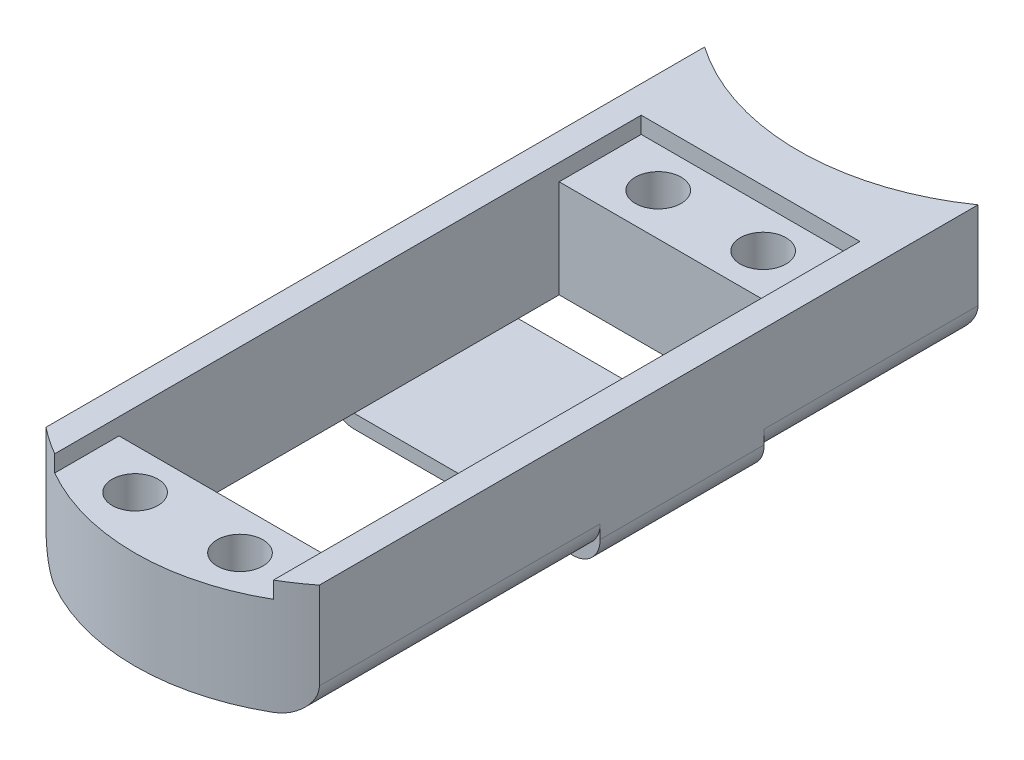
SolidWorks part; units mm, degrees
ref_plane "Front Plane" through (0, 0, 0) normal (0, 0, 1) x (1, 0, 0)
ref_plane "Top Plane" through (0, 0, 0) normal (0, 1, 0) x (1, 0, 0)
ref_plane "Right Plane" through (0, 0, 0) normal (1, 0, 0) x (0, 0, -1)
sketch "Sketch1" plane through (0, 0, 0) normal (0, 1, 0) x (1, 0, 0)
  circle A0 centre (0, 0) radius 20.3708 construction
  circle A1 centre (0, 0) radius 20.3708 construction
sketch "Sketch2" plane through (0, 0, 0) normal (0, 1, 0) x (1, 0, 0)
  line L0 (-12.7, 45.261) -> (-12.7, -15.9273)
  line L1 (-12.7, -8.89) -> (-12.7, -15.9273) construction
  line L2 (12.7, 45.261) -> (12.7, -15.9273)
  line L3 (-10.16, 29.21) -> (10.16, 29.21)
  line L4 (10.16, 29.21) -> (10.16, -17.6563)
  line L5 (-10.16, 29.21) -> (-10.16, -17.6563)
  circle A0 centre (0, 0) radius 20.3708 construction
  arc A1 (-10.16, -17.6563) -> (-12.7, -15.9273) centre (0, 0) cw
  arc A2 (10.16, -17.6563) -> (12.7, -15.9273) centre (0, 0) ccw
  arc A3 (-12.7, 45.261) -> (12.7, 45.261) centre (0, 63.5) ccw
  arc A4 (12.7, 45.261) -> (-12.7, 45.261) centre (0, 63.5) ccw construction
  point P27 (-10.16, -17.6563)
extrude "Boss-Extrude1" add sketch "Sketch2" against normal blind 10.6502
sketch "Sketch3" plane through (0, 0, 0) normal (0, 1, 0) x (1, 0, 0)
  line L1 (-10.16, 36.83) -> (10.16, 36.83)
  line L2 (-10.16, 36.83) -> (-10.16, 29.21)
  line L3 (-10.16, 29.21) -> (10.16, 29.21)
  line L4 (10.16, 36.83) -> (10.16, 29.21)
extrude "Cut-Extrude1" cut sketch "Sketch3" against normal blind 1.5494
sketch "Sketch4" plane through (0, -1.5494, 0) normal (0, 1, 0) x (1, 0, 0)
  circle A0 centre (-4.8743, 33.1241) radius 2.126
  circle A1 centre (4.8743, 33.1241) radius 2.126
  dimension "D1" = 4.252
  dimension "D2" = 4.252
extrude "Cut-Extrude2" cut sketch "Sketch4" against normal blind 19.3294
sketch "Sketch5" plane through (0, -1.5494, 0) normal (0, 1, 0) x (1, 0, 0)
  line L3 (10.16, -11.684) -> (-10.16, -11.684)
  line L12 (-10.16, -11.684) -> (-10.16, -17.6563)
  line L13 (10.16, -17.6563) -> (10.16, -11.684)
  line L14 (10.16, -11.684) -> (-10.16, -11.684)
  line L15 (-10.16, -11.684) -> (-10.16, -17.6563)
  line L16 (10.16, -17.6563) -> (10.16, -11.684)
  circle A0 centre (4.8743, -15.4762) radius 2.126 construction
  arc A1 (-10.16, -17.6563) -> (10.16, -17.6563) centre (0, 0) ccw
  arc A2 (-10.16, -17.6563) -> (10.16, -17.6563) centre (0, 0) ccw
  circle A3 centre (-4.8743, -15.4762) radius 2.126 construction
  circle A4 centre (4.8743, -15.4762) radius 2.126
  circle A5 centre (-4.8743, -15.4762) radius 2.126
  dimension "D2" = 0
extrude "Boss-Extrude2" add sketch "Sketch5" against normal up to surface (9.1008 mm away) up to face at (-4.8743, -10.6502, -30.9982)
ref_plane "Plane1" through (0, 0, -10.16) normal (0, 0, 1) x (1, 0, 0)
sketch "Sketch6" plane through (0, 0, -10.16) normal (0, 0, 1) x (1, 0, 0)
  line L0 (12.7, -10.6502) -> (12.7, 0) construction
  line L1 (-12.7, -10.6502) -> (12.7, -10.6502)
  line L2 (-12.7, -10.6502) -> (-12.7, -11.9202)
  line L3 (-12.7, -11.9202) -> (12.7, -11.9202)
  line L4 (12.7, -10.6502) -> (12.7, -11.9202)
  dimension "D1" = 1.27
extrude "Boss-Extrude3" add sketch "Sketch6" against normal blind 15.24
fillet "Fillet1" radius 2.54 4 edges at (12.7, -10.6502, 2.8837) (-12.7, -10.6502, 2.8837) (-12.7, -10.6502, -35.3305) (12.7, -10.6502, -35.3305)
fillet "Fillet2" radius 2.54 2 edges at (12.7, -11.9202, -17.78) (-12.7, -11.9202, -17.78)
